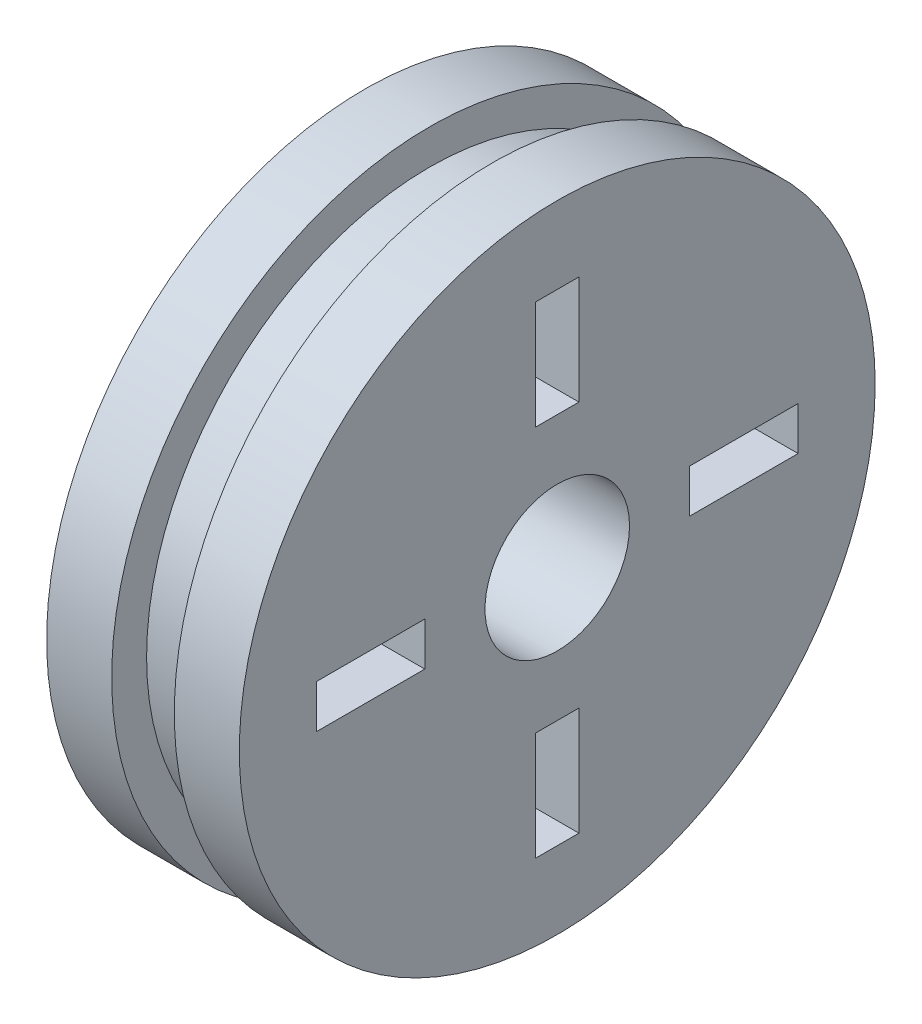
SolidWorks part; units mm, degrees
ref_plane "Front Plane" through (0, 0, 0) normal (0, 0, 1) x (1, 0, 0)
ref_plane "Top Plane" through (0, 0, 0) normal (0, 1, 0) x (1, 0, 0)
ref_plane "Right Plane" through (0, 0, 0) normal (1, 0, 0) x (0, 0, -1)
sketch "Sketch1" plane through (0, 0, 0) normal (1, 0, 0) x (0, 0, -1)
  circle A0 centre (52, -65) radius 13.2
extrude "Boss-Extrude1" add sketch "Sketch1" along normal blind 8 from offset 77.2
sketch "Sketch2" plane through (0, 0, 0) normal (1, 0, 0) x (0, 0, -1)
  circle A0 centre (52, -65) radius 20
extrude "Boss-Extrude2" add sketch "Sketch2" along normal blind 2.6 from offset 79.9 separate body
combine bodies "Combine1" operation type subtract main body 101 bodies to subtract 102
sketch "Sketch3" plane through (0, 0, 0) normal (1, 0, 0) x (0, 0, -1)
  circle A0 centre (52, -65) radius 11.75
extrude "Boss-Extrude3" add sketch "Sketch3" along normal blind 2.6 from offset 79.9
sketch "Sketch4" plane through (0, 0, 0) normal (1, 0, 0) x (0, 0, -1)
  circle A0 centre (52, -65) radius 4.6
extrude "Boss-Extrude4" add sketch "Sketch4" along normal blind 2.3 from offset 76.7 separate body
combine bodies "Combine2" operation type subtract main body 105 bodies to subtract 106
sketch "Sketch5" plane through (0, 0, 0) normal (0, 0, 1) x (1, 0, 0)
  line L1 (76.7, -65) -> (79, -65)
  line L2 (76.7, -65) -> (76.7, -53.5)
  line L3 (76.7, -53.5) -> (79, -53.5)
  line L4 (79, -65) -> (79, -53.5)
extrude "Boss-Extrude5" add sketch "Sketch5" along normal blind 6.6 from offset 55.3 separate body offset against normal yes
combine bodies "Combine3" operation type subtract main body 107 bodies to subtract 108
sketch "Sketch6" plane through (0, 0, 0) normal (0, 0, 1) x (1, 0, 0)
  line L1 (76.2, -59.5) -> (86.2, -59.5)
  line L2 (76.2, -59.5) -> (76.2, -55)
  line L3 (76.2, -55) -> (86.2, -55)
  line L4 (86.2, -59.5) -> (86.2, -55)
extrude "Boss-Extrude6" add sketch "Sketch6" along normal blind 1.8 from offset 52.9 separate body offset against normal yes
combine bodies "Combine4" operation type subtract main body 109 bodies to subtract 110
sketch "Sketch7" plane through (0, 0, 0) normal (0, 0, 1) x (1, 0, 0)
  line L1 (76.7, -76.5) -> (79, -76.5)
  line L2 (76.7, -76.5) -> (76.7, -65)
  line L3 (76.7, -65) -> (79, -65)
  line L4 (79, -76.5) -> (79, -65)
extrude "Boss-Extrude7" add sketch "Sketch7" along normal blind 6.6 from offset 55.3 separate body offset against normal yes
combine bodies "Combine5" operation type subtract main body 111 bodies to subtract 112
sketch "Sketch8" plane through (0, 0, 0) normal (0, 0, 1) x (1, 0, 0)
  line L1 (76.2, -75) -> (86.2, -75)
  line L2 (76.2, -75) -> (76.2, -70.5)
  line L3 (76.2, -70.5) -> (86.2, -70.5)
  line L4 (86.2, -75) -> (86.2, -70.5)
extrude "Boss-Extrude8" add sketch "Sketch8" along normal blind 1.8 from offset 52.9 separate body offset against normal yes
combine bodies "Combine6" operation type subtract main body 113 bodies to subtract 114
sketch "Sketch9" plane through (0, 0, 0) normal (0, 0, 1) x (1, 0, 0)
  line L1 (76.7, -68.3) -> (79, -68.3)
  line L2 (76.7, -68.3) -> (76.7, -61.7)
  line L3 (76.7, -61.7) -> (79, -61.7)
  line L4 (79, -68.3) -> (79, -61.7)
extrude "Boss-Extrude9" add sketch "Sketch9" along normal blind 11.5 from offset 52 separate body offset against normal yes
combine bodies "Combine7" operation type subtract main body 115 bodies to subtract 116
sketch "Sketch10" plane through (0, 0, 0) normal (0, 0, 1) x (1, 0, 0)
  line L1 (76.2, -65.9) -> (86.2, -65.9)
  line L2 (76.2, -65.9) -> (76.2, -64.1)
  line L3 (76.2, -64.1) -> (86.2, -64.1)
  line L4 (86.2, -65.9) -> (86.2, -64.1)
extrude "Boss-Extrude10" add sketch "Sketch10" along normal blind 4.5 from offset 46.5 separate body offset against normal yes
combine bodies "Combine8" operation type subtract main body 117 bodies to subtract 118
sketch "Sketch11" plane through (0, 0, 0) normal (0, 0, 1) x (1, 0, 0)
  line L1 (76.7, -68.3) -> (79, -68.3)
  line L2 (76.7, -68.3) -> (76.7, -61.7)
  line L3 (76.7, -61.7) -> (79, -61.7)
  line L4 (79, -68.3) -> (79, -61.7)
extrude "Boss-Extrude11" add sketch "Sketch11" along normal blind 11.5 from offset 63.5 separate body offset against normal yes
combine bodies "Combine9" operation type subtract main body 119 bodies to subtract 120
sketch "Sketch12" plane through (0, 0, 0) normal (0, 0, 1) x (1, 0, 0)
  line L1 (76.2, -65.9) -> (86.2, -65.9)
  line L2 (76.2, -65.9) -> (76.2, -64.1)
  line L3 (76.2, -64.1) -> (86.2, -64.1)
  line L4 (86.2, -65.9) -> (86.2, -64.1)
extrude "Boss-Extrude12" add sketch "Sketch12" along normal blind 4.5 from offset 62 separate body offset against normal yes
combine bodies "Combine10" operation type subtract main body 121 bodies to subtract 122
sketch "Sketch13" plane through (0, 0, 0) normal (1, 0, 0) x (0, 0, -1)
  circle A0 centre (52, -65) radius 3
extrude "Boss-Extrude13" add sketch "Sketch13" along normal blind 10 from offset 76.2 separate body
combine bodies "Combine11" operation type subtract main body 123 bodies to subtract 124
